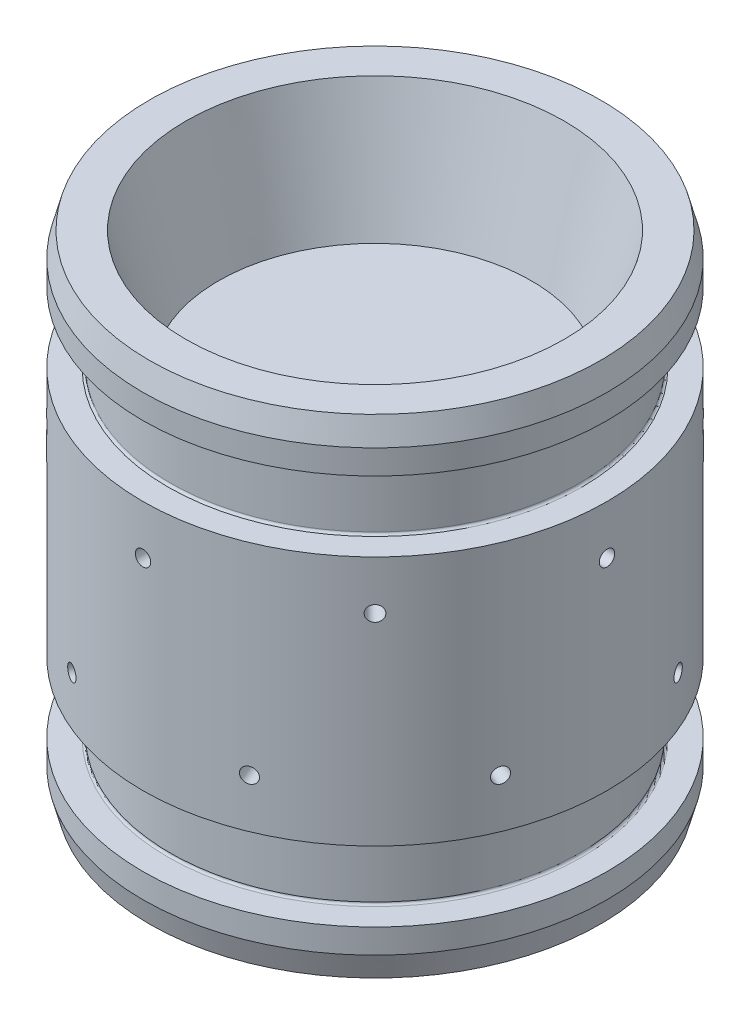
SolidWorks part; units mm, degrees
ref_plane "Front Plane" through (0, 0, 0) normal (0, 0, 1) x (1, 0, 0)
ref_plane "Top Plane" through (0, 0, 0) normal (0, 1, 0) x (1, 0, 0)
ref_plane "Right Plane" through (0, 0, 0) normal (1, 0, 0) x (0, 0, -1)
sketch "Sketch1" plane through (0, 0, 0) normal (0, 1, 0) x (1, 0, 0)
  circle A0 centre (0, 0) radius 24.1554
  dimension "D1" = 48.3108
extrude "body" add sketch "Sketch1" along normal mid plane 50.8
sketch "Sketch2" plane through (0, 25.4, 0) normal (0, 1, 0) x (1, 0, 0)
  circle A0 centre (0, 0) radius 15.875
  dimension "D1" = 31.75
extrude "\"lightening hole\"" cut sketch "Sketch2" against normal blind 12.7
sketch "main-o-ring" plane through (0, 0, 0) normal (0, 0, 1) x (1, 0, 0)
  line L0 (0, 0) -> (0, 33.5592) construction
  line L1 (-24.1554, 20.32) -> (-24.1554, 13.0302)
  line L2 (-24.1554, 20.32) -> (-21.5508, 20.32)
  line L3 (-21.3106, 20.0798) -> (-21.3106, 13.2704)
  line L4 (-21.5508, 13.0302) -> (-24.1554, 13.0302)
  line L5 (24.1554, 25.4) -> (-24.1554, 25.4) construction
  line L6 (-22.7942, 25.4) -> (-24.1554, 20.32) construction
  line L7 (-24.1554, 20.32) -> (-24.1554, 25.4) construction
  line L8 (-24.1554, 25.4) -> (-22.7942, 25.4) construction
  arc A0 (-21.3106, 13.2704) -> (-21.5508, 13.0302) centre (-21.5508, 13.2704) cw
  arc A1 (-21.5508, 20.32) -> (-21.3106, 20.0798) centre (-21.5508, 20.0798) cw
  dimension "D5" = 0.2402
  dimension "D1" = 48.3108
  dimension "D2" = 7.2898
  dimension "D3" = 5.08
  dimension "D4" = 2.8448
  dimension "D6" = 15
  dimension "D7" = 5.08
revolve "o-ring-main (with backup rings)" cut sketch "main-o-ring" angle 360 about L0
chamfer "install-chamfer" distance 2.54 angle 15 1 edges at (0, 25.4, 24.1554) first distance on face at (0, 25.4, 24.1554)
chamfer "prop-chamfer" distance 3.81 angle 75 1 edges at (0, 25.4, 15.875) first distance on face at (0, 25.4, 23.4748)
mirror "Top-Bottom Symmetry" about plane through (0, 0, 0) normal (0, 1, 0) of "o-ring-main (with backup rings)", "\"lightening hole\""
chamfer "bot-install-chamfer" distance 2.54 angle 15 1 edges at (0, -25.4, 24.1554) first distance on face at (0, -25.4, 24.1554)
chamfer "bot-prop-chamfer" distance 3.81 angle 75 1 edges at (0, -25.4, 15.875) first distance on face at (0, -25.4, 23.4748)
hole_wizard "M2x0.4 Tapped Hole (top)" positions "3DSketch1" profile "Sketch3" tap size "M2x0.4" standard "ANSI Metric"
sketch3d "3DSketch1"
  point P0 (-24.1554, 7.9375, 0)
  dimension "D1" = 7.9375
cosmetic thread "Hole Thread34" parameters "D1"=6.7564, "D2"=2
sketch "Sketch3" plane through (-24.1554, 7.9375, 0) normal (0, 1, 0) x (0, 0, 1)
  line L0 (0, 0) -> (0, 7.2371)
  line L1 (0, 7.2371) -> (0.8, 6.7564)
  line L2 (0.8, 6.7564) -> (0.8, 0)
  line L5 (0.8, 0) -> (0, 0)
  line L10 (0, 7.2371) -> (-0.8, 6.7564) construction
  line L11 (0, -6.35) -> (0, 107.95) construction
  dimension "Tap Drill Dia." = 1.6
  dimension "Tap Drill Depth" = 6.7564
  dimension "Drill Angle" = 118
ref_plane "Offset Reference" through (-22.3167, 0, -9.2439) normal (-0.9239, 0, -0.3827) x (0, -1, 0)
hole_wizard "M2x0.4 Tapped Hole (bottom)" positions "3DSketch2" profile "Sketch4" tap size "M2x0.4" standard "ANSI Metric"
sketch3d "3DSketch2"
  point P0 (-22.3167, -7.9375, -9.2439)
  dimension "D1" = 7.9375
sketch "Sketch4" plane through (-22.3167, -7.9375, -9.2439) normal (0, 1, 0) x (-0.3827, 0, 0.9239)
  line L0 (0, 0) -> (0, 7.2371)
  line L1 (0, 7.2371) -> (0.8, 6.7564)
  line L2 (0.8, 6.7564) -> (0.8, 0)
  line L5 (0.8, 0) -> (0, 0)
  line L10 (0, 7.2371) -> (-0.8, 6.7564) construction
  line L11 (0, -6.35) -> (0, 107.95) construction
  dimension "Tap Drill Dia." = 1.6
  dimension "Tap Drill Depth" = 6.7564
  dimension "Drill Angle" = 118
cosmetic thread "Hole Thread35" parameters "D1"=6.7564, "D2"=2
pattern_circular "Tapped Hole Pattern (8X)" count 8 over 360 about axis through (0, 25.4, 0) along (0, -1, 0) of "M2x0.4 Tapped Hole (top)", "M2x0.4 Tapped Hole (bottom)"
cosmetic thread "Hole Thread36" parameters "D1"=6.7564, "D2"=2
cosmetic thread "Hole Thread37" parameters "D1"=6.7564, "D2"=2
cosmetic thread "Hole Thread38" parameters "D1"=6.7564, "D2"=2
cosmetic thread "Hole Thread39" parameters "D1"=6.7564, "D2"=3.5052
cosmetic thread "Hole Thread40" parameters "D1"=6.7564, "D2"=3.5052
cosmetic thread "Hole Thread41" parameters "D1"=6.7564, "D2"=2
cosmetic thread "Hole Thread42" parameters "D1"=6.7564, "D2"=3.5052
cosmetic thread "Hole Thread43" parameters "D1"=6.7564, "D2"=2
cosmetic thread "Hole Thread44" parameters "D1"=6.7564, "D2"=2
cosmetic thread "Hole Thread45" parameters "D1"=6.7564, "D2"=3.5052
cosmetic thread "Hole Thread46" parameters "D1"=6.7564, "D2"=3.5052
cosmetic thread "Hole Thread47" parameters "D1"=6.7564, "D2"=3.5052
cosmetic thread "Hole Thread48" parameters "D1"=6.7564, "D2"=3.5052
cosmetic thread "Hole Thread49" parameters "D1"=6.7564, "D2"=2
cosmetic thread "Hole Thread76" parameters "D1"=6.7564, "D2"=2
cosmetic thread "Hole Thread77" parameters "D1"=6.7564, "D2"=2
cosmetic thread "Hole Thread78" parameters "D1"=6.7564, "D2"=2
cosmetic thread "Hole Thread79" parameters "D1"=6.7564, "D2"=2
cosmetic thread "Hole Thread80" parameters "D1"=6.7564, "D2"=2
cosmetic thread "Hole Thread81" parameters "D1"=6.7564, "D2"=2
cosmetic thread "Hole Thread82" parameters "D1"=6.7564, "D2"=2
ref_plane "Plane1" [suppressed] through (0, -12.7, 0) normal (-1, 0, 0) x (0, 0, -1)
ref_plane "Plane2" [suppressed] through (0, 12.7, 0) normal (-1, 0, 0) x (0, 0, 1)
ref_plane "Plane3" [suppressed] through (0, 12.7, 0) normal (-1, 0, 0) x (0, 0, 1)
ref_plane "Plane4" [suppressed] through (0, -3.81, 0) normal (-1, 0, 0) x (0, 0, 1)
ref_plane "Plane6" [suppressed] through (-15.24, -3.81, 0) normal (-1, 0, 0) x (0, 0, 1)
ref_plane "Plane7" [suppressed] through (-10.16, 12.7, 0) normal (-1, 0, 0) x (0, 0, 1)
ref_plane "Plane8" [suppressed] through (-10.16, 12.7, 0) normal (-1, 0, 0) x (0, 0, 1)
ref_plane "Plane9" [suppressed] through (0, -12.7, 0) normal (-1, 0, 0) x (0, 0, -1)
ref_plane "Plane10" [suppressed] through (7.112, -12.7, 0) normal (-1, 0, 0) x (0, 0, -1)
ref_plane "Plane11" [suppressed] through (0, 0, 0) normal (-1, 0, 0) x (0, 0, 1)
ref_plane "Plane12" [suppressed] through (0, 25.4, 0) normal (-1, 0, 0) x (0, 0, -1)
ref_plane "Plane13" [suppressed] through (-12.456, 12.7, -2.4776) normal (-1, 0, 0) x (0, 0, 1)
ref_plane "Plane14" [suppressed] through (-12.456, 12.7, -2.4776) normal (-1, 0, 0) x (0, 0, 1)
